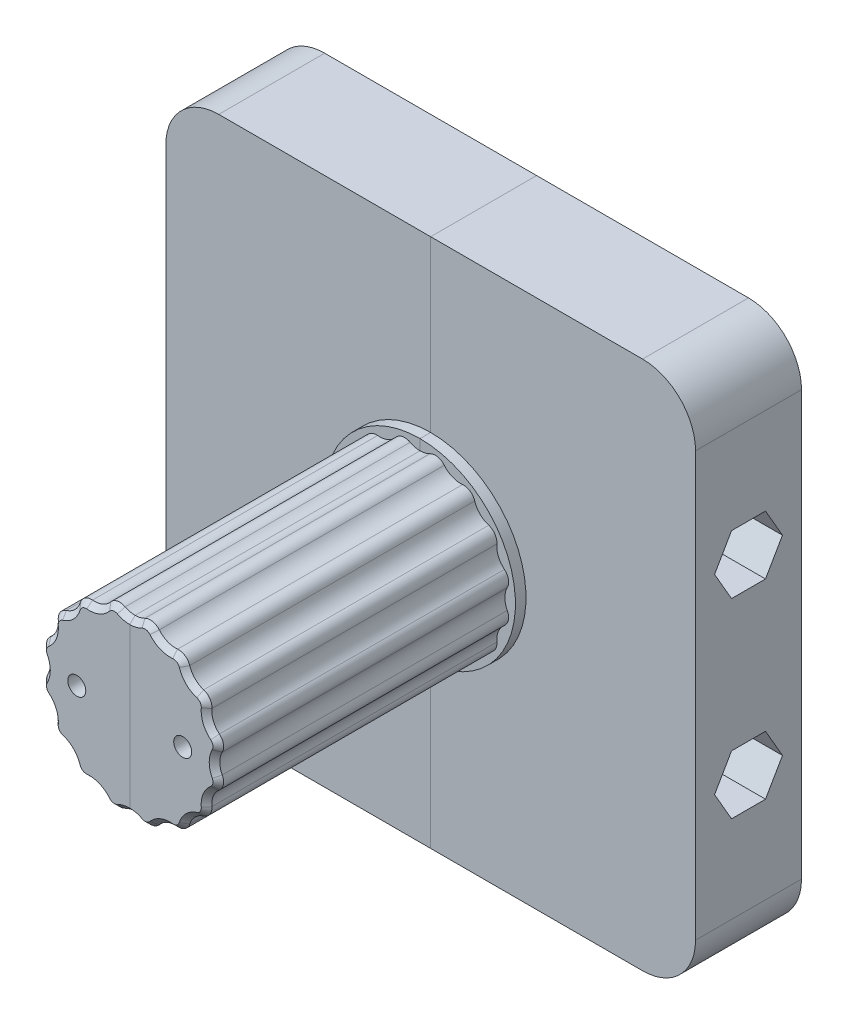
SolidWorks part; units mm, degrees
ref_plane "Plan de face" through (0, 0, 0) normal (0, 0, 1) x (1, 0, 0)
ref_plane "Plan de dessus" through (0, 0, 0) normal (0, 1, 0) x (1, 0, 0)
ref_plane "Plan de droite" through (0, 0, 0) normal (1, 0, 0) x (0, 0, -1)
sketch "Esquisse1" plane through (0, 0, 0) normal (0, 0, 1) x (1, 0, 0)
  line L1 (-25, -25) -> (25, -25)
  line L2 (-25, -25) -> (-25, 25)
  line L3 (-25, 25) -> (25, 25)
  line L4 (25, -25) -> (25, 25)
  line L5 (-25, -25) -> (25, 25) construction
  line L6 (-25, 25) -> (25, -25) construction
  point P0 (0, 0)
  dimension "D2" = 50
  dimension "D3" = 50
extrude "Boss.-Extru.1" add sketch "Esquisse1" along normal blind 10
sketch "Esquisse2" plane through (0, 0, 10) normal (0, 0, 1) x (1, 0, 0)
  circle A0 centre (0, 0) radius 9
  dimension "D1" = 18
extrude "Boss.-Extru.2" add sketch "Esquisse2" along normal blind 1
sketch "Esquisse5" plane through (0, 0, 10) normal (0, 0, 1) x (1, 0, 0)
  circle A0 centre (0, 0) radius 8.5
  dimension "D1" = 17
extrude "Boss.-Extru.3" add sketch "Esquisse5" along normal blind 27.4 from surface starting at face at (9, 0, 11)
sketch "Esquisse6" [suppressed] plane through (0, 0, 22) normal (0, 0, 1) x (1, 0, 0)
  line L0 (0, 2.5) -> (0, -2.5) construction
  line L1 (-1.5, 2) -> (-1.5, -2) construction
  line L3 (1.5, 2) -> (1.5, -2) construction
  line L4 (-1.6, 2.0494) -> (-1.6, -2.0494)
  line L5 (1.6, 2.0494) -> (1.6, -2.0494)
  arc A0 (-1.5, -2) -> (1.5, -2) centre (0, 0) ccw construction
  arc A1 (1.5, 2) -> (-1.5, 2) centre (0, 0) ccw construction
  arc A2 (-1.6, -2.0494) -> (1.6, -2.0494) centre (0, 0) ccw
  arc A3 (1.6, 2.0494) -> (-1.6, 2.0494) centre (0, 0) ccw
  dimension "D2" = 5
  dimension "D1" = 1.5
  dimension "D3" = 0.1
extrude "Enlèv. mat.-Extru.1" [suppressed] cut sketch "Esquisse6" against normal up to surface (12 mm away) up to face at (9, 0, 10)
sketch "Esquisse15" plane through (0, 0, 38.4) normal (0, 0, 1) x (1, 0, 0)
  line L0 (-1.3775, 1.45) -> (1.3775, 1.45) construction
  line L1 (-1.4169, 1.55) -> (1.4169, 1.55)
  arc A0 (-1.3775, 1.45) -> (1.3775, 1.45) centre (0, 0) ccw construction
  arc A1 (-1.4169, 1.55) -> (1.4169, 1.55) centre (0, 0) ccw
  point P5 (0, -2)
  dimension "D1" = 4
  dimension "D2" = 3.45
  dimension "D3" = 0.1
extrude "Enlèv. mat.-Extru.8" [suppressed] cut sketch "Esquisse15" against normal blind 10
sketch "Esquisse16" plane through (0, 0, 38.4) normal (0, 0, 1) x (1, 0, 0)
  line L0 (-5, 0) -> (5, 0) construction
  circle A0 centre (-5, 0) radius 0.85
  circle A1 centre (5, 0) radius 0.85
  point P4 (0, 0)
  dimension "D1" = 1.7
  dimension "D2" = 10
extrude "Enlèv. mat.-Extru.9" cut sketch "Esquisse16" against normal blind 10
sketch "Esquisse7" plane through (0, 0, 38.4) normal (0, 0, 1) x (1, 0, 0)
  arc A0 (-0.9333, 8.2311) -> (0.9333, 8.2311) centre (0, 10) ccw
  circle A1 centre (0, 0) radius 8.5 construction
  circle A2 centre (0, 0) radius 8.5 construction
  circle A3 centre (0, 0) radius 8.5 construction
  arc A4 (2.2876, 7.9617) -> (4.0122, 7.2474) centre (3.8268, 9.2388) ccw
  arc A5 (5.1603, 6.4802) -> (6.4802, 5.1603) centre (7.0711, 7.0711) ccw
  arc A6 (7.2474, 4.0122) -> (7.9617, 2.2876) centre (9.2388, 3.8268) ccw
  arc A7 (8.2311, 0.9333) -> (8.2311, -0.9333) centre (10, 0) ccw
  arc A8 (7.9617, -2.2876) -> (7.2474, -4.0122) centre (9.2388, -3.8268) ccw
  arc A9 (6.4802, -5.1603) -> (5.1603, -6.4802) centre (7.0711, -7.0711) ccw
  arc A10 (4.0122, -7.2474) -> (2.2876, -7.9617) centre (3.8268, -9.2388) ccw
  arc A11 (0.9333, -8.2311) -> (-0.9333, -8.2311) centre (0, -10) ccw
  arc A12 (-2.2876, -7.9617) -> (-4.0122, -7.2474) centre (-3.8268, -9.2388) ccw
  arc A13 (-5.1603, -6.4802) -> (-6.4802, -5.1603) centre (-7.0711, -7.0711) ccw
  arc A14 (-7.2474, -4.0122) -> (-7.9617, -2.2876) centre (-9.2388, -3.8268) ccw
  arc A15 (-8.2311, -0.9333) -> (-8.2311, 0.9333) centre (-10, 0) ccw
  arc A16 (-7.9617, 2.2876) -> (-7.2474, 4.0122) centre (-9.2388, 3.8268) ccw
  arc A17 (-6.4802, 5.1603) -> (-5.1603, 6.4802) centre (-7.0711, 7.0711) ccw
  arc A18 (-4.0122, 7.2474) -> (-2.2876, 7.9617) centre (-3.8268, 9.2388) ccw
  arc A19 (2.2876, 7.9617) -> (0.9333, 8.2311) centre (1.4445, 7.2622) ccw
  arc A20 (5.1603, 6.4802) -> (4.0122, 7.2474) centre (4.1137, 6.1566) ccw
  arc A21 (7.2474, 4.0122) -> (6.4802, 5.1603) centre (6.1566, 4.1137) ccw
  arc A22 (8.2311, 0.9333) -> (7.9617, 2.2876) centre (7.2622, 1.4445) ccw
  arc A23 (7.9617, -2.2876) -> (8.2311, -0.9333) centre (7.2622, -1.4445) ccw
  arc A24 (6.4802, -5.1603) -> (7.2474, -4.0122) centre (6.1566, -4.1137) ccw
  arc A25 (4.0122, -7.2474) -> (5.1603, -6.4802) centre (4.1137, -6.1566) ccw
  arc A26 (0.9333, -8.2311) -> (2.2876, -7.9617) centre (1.4445, -7.2622) ccw
  arc A27 (-2.2876, -7.9617) -> (-0.9333, -8.2311) centre (-1.4445, -7.2622) ccw
  arc A28 (-5.1603, -6.4802) -> (-4.0122, -7.2474) centre (-4.1137, -6.1566) ccw
  arc A29 (-7.2474, -4.0122) -> (-6.4802, -5.1603) centre (-6.1566, -4.1137) ccw
  arc A30 (-8.2311, -0.9333) -> (-7.9617, -2.2876) centre (-7.2622, -1.4445) ccw
  arc A31 (-7.9617, 2.2876) -> (-8.2311, 0.9333) centre (-7.2622, 1.4445) ccw
  arc A32 (-6.4802, 5.1603) -> (-7.2474, 4.0122) centre (-6.1566, 4.1137) ccw
  arc A33 (-4.0122, 7.2474) -> (-5.1603, 6.4802) centre (-4.1137, 6.1566) ccw
  arc A34 (-0.9333, 8.2311) -> (-2.2876, 7.9617) centre (-1.4445, 7.2622) ccw
  circle A37 centre (0, 0) radius 9.904
  point P2 (0, 8)
  point P5 (0, 8.5)
  point P43 (0, 0)
  point P75 (0, 0)
  dimension "D1" = 4
  dimension "D2" = 0.5
  dimension "D3" = 16
  dimension "D4" = 16
extrude "Enlèv. mat.-Extru.2" cut sketch "Esquisse7" against normal up to surface (27.4 mm away) up to face at (8.5, 0, 11)
chamfer "Chanfrein1" distance 0.5 angle 45 32 edges at (3.0615, 7.391, 38.4) (1.6583, 8.3367, 38.4) (4.7223, 7.0675, 38.4) (0, 8, 38.4) (5.6569, 5.6569, 38.4) (-1.6583, 8.3367, 38.4) (7.0675, 4.7223, 38.4) (-3.0615, 7.391, 38.4) (7.391, 3.0615, 38.4) (-4.7223, 7.0675, 38.4) (8.3367, 1.6583, 38.4) (-5.6569, 5.6569, 38.4) (8, 0, 38.4) (-7.0675, 4.7223, 38.4) (8.3367, -1.6583, 38.4) (-7.391, 3.0615, 38.4) (7.391, -3.0615, 38.4) (-8.3367, 1.6583, 38.4) (7.0675, -4.7223, 38.4) (-8, 0, 38.4) (5.6569, -5.6569, 38.4) (-8.3367, -1.6583, 38.4) (4.7223, -7.0675, 38.4) (-7.391, -3.0615, 38.4) (3.0615, -7.391, 38.4) (-7.0675, -4.7223, 38.4) (1.6583, -8.3367, 38.4) (-5.6569, -5.6569, 38.4) (0, -8, 38.4) (-4.7223, -7.0675, 38.4) (-1.6583, -8.3367, 38.4) (-3.0615, -7.391, 38.4)
sketch "Esquisse8" plane through (0, 0, 0) normal (0, 0, -1) x (-1, 0, 0)
  line L4 (-25, 25) -> (-25, -25)
  line L5 (-25, -25) -> (25, -25)
  line L6 (25, -25) -> (25, 25)
  line L7 (25, 25) -> (-25, 25)
  line L8 (-25, 25) -> (-25, -25)
  line L9 (-25, -25) -> (25, -25)
  line L10 (25, -25) -> (25, 25)
  line L11 (25, 25) -> (-25, 25)
  dimension "D1" = 0
extrude "Enlèv. mat.-Extru.3" [suppressed] cut sketch "Esquisse8" against normal offset from surface (2 mm away) 3 up to face at (9, 0, 10)
sketch "Esquisse9" [suppressed] plane through (0, 0, 2) normal (0, 0, -1) x (-1, 0, 0)
  line L4 (25, 25) -> (-25, 25)
  line L5 (-25, 25) -> (-25, -25)
  line L6 (-25, -25) -> (25, -25)
  line L7 (25, -25) -> (25, 25)
  line L8 (25, 25) -> (-25, 25)
  line L9 (-25, 25) -> (-25, -25)
  line L10 (-25, -25) -> (25, -25)
  line L11 (25, -25) -> (25, 25)
  circle A0 centre (0, 0) radius 22.5
  dimension "D1" = 45
  dimension "D2" = 0
extrude "Enlèv. mat.-Extru.4" [suppressed] cut sketch "Esquisse9" against normal blind 3
fillet "Congé1" radius 5 4 edges at (-25, -25, 5) (-25, 25, 5) (25, 25, 5) (25, -25, 5)
sketch "Esquisse10" plane through (0, 0, 0) normal (0, 0, -1) x (-1, 0, 0)
  circle A0 centre (0, 0) radius 2.15
  dimension "D1" = 4.3
extrude "Enlèv. mat.-Extru.5" cut sketch "Esquisse10" against normal blind 8
split "Fractionner1" bodies to split 109 resulting bodies 112 113 split by face at (-2.15, 0, 8)
sketch "Esquisse13" plane through (0, 0, 0) normal (0, 0, -1) x (-1, 0, 0)
  circle A0 centre (0, 0) radius 2.15 construction
  circle A1 centre (0, 0) radius 2.15
curve "Hélice/Spirale1" pitch 1.27 height 10 radius 2.15 centre (0, 0, 0) axis (0, 0, 1) start towards (-1, 0, 0)
chamfer "Chanfrein3" distance 1.5 angle 45 1 edges at (-2.15, 0, 0)
sketch "Esquisse14" plane through (0, 0, 0) normal (0, 1, 0) x (1, 0, 0)
  line L0 (0, -12.1883) -> (0, 6.2203) construction
  line L1 (-2.15, -11.7343) -> (-2.15, 4.6609) construction
  line L2 (-20, 0) -> (20, 0) construction
  line L3 (-2.15, 0.3175) -> (-2.8374, 0.7144) construction
  line L4 (-2.8374, 0.7144) -> (-2.8374, 0.8731) construction
  line L5 (-2.8374, 0.8731) -> (-2.15, 1.27) construction
  line L6 (-2.15, 1.27) -> (-2.15, 0.3175) construction
  line L7 (-1.95, 1.6164) -> (-1.95, 0)
  line L8 (-2.35, 0.202) -> (-3.0374, 0.5989)
  line L10 (-3.0374, 0.9886) -> (-1.95, 1.6164)
  line L11 (-2.35, 0) -> (-2.35, 0.202)
  line L12 (-2.35, 0) -> (-1.95, 0)
  line L13 (-2.35, -11.7343) -> (-2.35, 2.9925) construction
  line L14 (-1.95, -0.0289) -> (-3.0374, 0.5989) construction
  line L15 (-1.95, 1.6164) -> (-1.95, -0.0289) construction
  line L16 (-2.15, -11.7343) -> (-2.15, 2.9925) construction
  line L17 (-3.0374, 0.5989) -> (-3.0374, 0.9886) construction
  arc A0 (-3.0374, 0.5989) -> (-3.0374, 0.9886) centre (-2.9249, 0.7938) cw
  spline S0 degree 3 poles (-2.15, 0) (-2.15, -0.0265) (-2.0363, -0.0801) (-1.5508, -0.16) (-0.8256, -0.24) (0.0273, -0.32) (0.876, -0.4) (1.5892, -0.48) (2.0567, -0.56) (2.2062, -0.64) (2.0146, -0.72) (1.5115, -0.8) (0.7747, -0.88) (-0.0819, -0.96) (-0.9258, -1.04) (-1.6266, -1.12) (-2.0758, -1.2) (-2.2042, -1.28) (-1.9917, -1.36) (-1.4713, -1.44) (-0.7234, -1.52) (0.1364, -1.6) (0.9751, -1.68) (1.663, -1.76) (2.0937, -1.84) (2.2008, -1.92) (1.9676, -2) (1.4301, -2.08) (0.6716, -2.16) (-0.1908, -2.24) (-1.0237, -2.32) (-1.6983, -2.4) (-2.1104, -2.48) (-2.1961, -2.56) (-1.9422, -2.64) (-1.3881, -2.72) (-0.6194, -2.8) (0.2452, -2.88) (1.0718, -2.96) (1.7327, -3.04) (2.1257, -3.12) (2.19, -3.2) (1.9157, -3.28) (1.3453, -3.36) (0.5668, -3.44) (-0.2993, -3.52) (-1.1192, -3.6) (-1.7659, -3.68) (-2.1397, -3.76) (-2.1826, -3.84) (-1.8881, -3.92) (-1.3016, -4) (-0.5139, -4.08) (0.3533, -4.16) (1.1659, -4.24) (1.7981, -4.32) (2.1524, -4.4) (2.1739, -4.48) (1.8592, -4.56) (1.2571, -4.64) (0.4606, -4.72) (-0.4071, -4.8) (-1.2118, -4.88) (-1.8292, -4.96) (-2.1638, -5.04) (-2.1638, -5.12) (-1.8292, -5.2) (-1.2118, -5.28) (-0.4071, -5.36) (0.4606, -5.44) (1.2571, -5.52) (1.8592, -5.6) (2.1739, -5.68) (2.1524, -5.76) (1.7981, -5.84) (1.1659, -5.92) (0.3533, -6) (-0.5139, -6.08) (-1.3016, -6.16) (-1.8881, -6.24) (-2.1826, -6.32) (-2.1397, -6.4) (-1.7659, -6.48) (-1.1192, -6.56) (-0.2993, -6.64) (0.5668, -6.72) (1.3453, -6.8) (1.9157, -6.88) (2.19, -6.96) (2.1257, -7.04) (1.7327, -7.12) (1.0718, -7.2) (0.2452, -7.28) (-0.6194, -7.36) (-1.3881, -7.44) (-1.9422, -7.52) (-2.1961, -7.6) (-2.1104, -7.68) (-1.6983, -7.76) (-1.0237, -7.84) (-0.1908, -7.92) (0.6716, -8) (1.4301, -8.08) (1.9676, -8.16) (2.2008, -8.24) (2.0937, -8.32) (1.663, -8.4) (0.9751, -8.48) (0.1364, -8.56) (-0.7234, -8.64) (-1.4713, -8.72) (-1.9917, -8.8) (-2.2042, -8.88) (-2.0758, -8.96) (-1.6266, -9.04) (-0.9258, -9.12) (-0.0819, -9.2) (0.7747, -9.28) (1.5115, -9.36) (2.0146, -9.44) (2.2062, -9.52) (2.0567, -9.6) (1.5892, -9.68) (0.876, -9.76) (0.0271, -9.84) (-0.825, -9.9199) (-1.3103, -9.9735) (-1.5108, -10) knots 0 0 0 0 0.008 0.016 0.024 0.032 0.04 0.048 0.056 0.064 0.072 0.08 0.088 0.096 0.104 0.112 0.12 0.128 0.136 0.144 0.152 0.16 0.168 0.176 0.184 0.192 0.2 0.208 0.216 0.224 0.232 0.24 0.248 0.256 0.264 0.272 0.28 0.288 0.296 0.304 0.312 0.32 0.328 0.336 0.344 0.352 0.36 0.368 0.376 0.384 0.392 0.4 0.408 0.416 0.424 0.432 0.44 0.448 0.456 0.464 0.472 0.48 0.488 0.496 0.504 0.512 0.52 0.528 0.536 0.544 0.552 0.56 0.568 0.576 0.584 0.592 0.6 0.608 0.616 0.624 0.632 0.64 0.648 0.656 0.664 0.672 0.68 0.688 0.696 0.704 0.712 0.72 0.728 0.736 0.744 0.752 0.76 0.768 0.776 0.784 0.792 0.8 0.808 0.816 0.824 0.832 0.84 0.848 0.856 0.864 0.872 0.88 0.888 0.896 0.904 0.912 0.92 0.928 0.936 0.944 0.952 0.96 0.968 0.976 0.984 0.992 1 1 1 1 construction
  point P5 (-2.15, 0)
  point P24 (-2.3, 4.6609)
  point P27 (0, 0)
  point P28 (0, 0)
  dimension "D1" = 60
  dimension "D2" = 1.27
  dimension "D3" = 0.3175
  dimension "D4" = 0.1588
  dimension "D5" = 0.2
  dimension "D6" = 0.2
sweep "Enlèvement de matière-Balayage1" cut profiles "Esquisse14" path "Hélice/Spirale1" align with end faces yes
combine bodies "Combiner1" operation type add bodies to combine 114 113
sketch "Esquisse11" plane through (0, 0, 0) normal (0, 0, -1) x (-1, 0, 0)
  circle A0 centre (0, 14) radius 2.25
  dimension "D1" = 4.5
  dimension "D2" = 14
extrude "Enlèv. mat.-Extru.6" cut sketch "Esquisse11" against normal blind 5
chamfer "Chanfrein2" distance 2 angle 45 1 edges at (-2.25, 14, 5)
chamfer "Chanfrein4" distance 1 angle 45 1 edges at (-2.25, 14, 0)
sketch "Esquisse12" plane through (0, 0, 10) normal (0, 0, 1) x (1, 0, 0)
  line L4 (-25, 20) -> (-25, -20)
  line L5 (-20, -25) -> (20, -25)
  line L6 (25, -20) -> (25, 20)
  line L7 (20, 25) -> (-20, 25)
  line L8 (-25, 20) -> (-25, -20)
  line L9 (-20, -25) -> (20, -25)
  line L10 (25, -20) -> (25, 20)
  line L11 (20, 25) -> (-20, 25)
  arc A4 (-25, -20) -> (-20, -25) centre (-20, -20) ccw
  arc A5 (20, -25) -> (25, -20) centre (20, -20) ccw
  arc A6 (25, 20) -> (20, 25) centre (20, 20) ccw
  arc A7 (-20, 25) -> (-25, 20) centre (-20, 20) ccw
  arc A8 (-25, -20) -> (-20, -25) centre (-20, -20) ccw
  arc A9 (20, -25) -> (25, -20) centre (20, -20) ccw
  arc A10 (25, 20) -> (20, 25) centre (20, 20) ccw
  arc A11 (-20, 25) -> (-25, 20) centre (-20, 20) ccw
  dimension "D1" = 0
extrude "Enlèv. mat.-Extru.7" [suppressed] cut sketch "Esquisse12" against normal through all
sketch "Sketch3" plane through (0, 0, 38.4) normal (0, 0, 1) x (1, 0, 0)
  circle A0 centre (0, 0) radius 4.6
  circle A1 centre (0, 0) radius 3
  dimension "D1" = 9.2
  dimension "D2" = 6
sketch "Sketch1" plane through (0, 0, 38.4) normal (0, 0, 1) x (1, 0, 0)
  circle A0 centre (0, 0) radius 3
  dimension "D1" = 6
extrude "Cut-Extrude1" [suppressed] cut sketch "Sketch1" against normal blind 6.1 from surface
sketch "Sketch2" plane through (0, 0, 0) normal (0, 0, 1) x (1, 0, 0)
  circle A0 centre (0, 0) radius 8.5
  arc A1 (8.2311, 0.9333) -> (7.9617, 2.2876) centre (7.2622, 1.4445) ccw construction
extrude "Boss-Extrude1" [suppressed] add sketch "Sketch2" against normal blind 2 from surface
fillet "Fillet1" [suppressed] radius 0.6
sketch "Sketch4" plane through (0, 0, 0) normal (0, 0, -1) x (-1, 0, 0)
  line L12 (-9, -9) -> (9, -9)
  line L13 (9, -9) -> (9, 9)
  line L14 (9, 9) -> (-9, 9)
  line L15 (-9, 9) -> (-9, -9)
  line L16 (-4, -9) -> (4, -9)
  line L17 (9, -4) -> (9, 4)
  line L18 (4, 9) -> (-4, 9)
  line L19 (-9, 4) -> (-9, -4)
  arc A8 (-4, -9) -> (-9, -4) centre (-4, -4) cw
  arc A9 (4, -9) -> (9, -4) centre (4, -4) ccw
  arc A10 (9, 4) -> (4, 9) centre (4, 4) ccw
  arc A11 (-4, 9) -> (-9, 4) centre (-4, 4) ccw
  dimension "D2" = 5
  dimension "D1" = 16
extrude "Cut-Extrude3" cut sketch "Sketch4" against normal blind 1
sketch "Sketch5" plane through (0, 0, 0) normal (1, 0, 0) x (0, 0, -1)
  line L0 (-5, 25) -> (-5, -25) construction
  line L1 (-10, 25) -> (0, 25) construction
  line L2 (0, -25) -> (-10, -25) construction
  line L3 (0, 0) -> (-37.9, 0) construction
  line L4 (-37.9, 0.9333) -> (-37.9, -0.9333) construction
  line L6 (-8.2043, 9) -> (-6.6021, 6.225)
  line L7 (-6.6021, 6.225) -> (-3.3979, 6.225)
  line L8 (-3.3979, 6.225) -> (-1.7957, 9)
  line L9 (-1.7957, 9) -> (-3.3979, 11.775)
  line L10 (-3.3979, 11.775) -> (-6.6021, 11.775)
  line L11 (-6.6021, 11.775) -> (-8.2043, 9)
  line L12 (-8.2043, -9) -> (-6.6021, -11.775)
  line L13 (-6.6021, -11.775) -> (-3.3979, -11.775)
  line L14 (-3.3979, -11.775) -> (-1.7957, -9)
  line L15 (-1.7957, -9) -> (-3.3979, -6.225)
  line L16 (-3.3979, -6.225) -> (-6.6021, -6.225)
  line L17 (-6.6021, -6.225) -> (-8.2043, -9)
  circle A0 centre (-5, 19) radius 0.9
  circle A1 centre (-5, -19) radius 0.9
  circle A2 centre (-5, 9) radius 1.6
  circle A3 centre (-5, -9) radius 1.6
  circle A4 centre (-33.9, 0) radius 0.9
  circle A5 centre (-18.9, 0) radius 0.9
  circle A6 centre (-5, 9) radius 3
  circle A7 centre (-5, -9) radius 3
  circle A8 centre (-5, 9) radius 2.775 construction
  circle A9 centre (-5, -9) radius 2.775 construction
  point P6 (-5, 0)
  dimension "D3" = 1.8
  dimension "D8" = 3.2
  dimension "D9" = 6
  dimension "D1" = 19
  dimension "D2" = 19
  dimension "D4" = 9
  dimension "D5" = 9
  dimension "D6" = 15
  dimension "D7" = 4
  dimension "D10" = 5.55
extrude "Cut-Extrude4" cut sketch "Sketch5" against normal mid plane 7 contours A4 | A5
extrude "Cut-Extrude6" cut sketch "Sketch5<4>" against normal mid plane 20 contours A2 | A3
sketch "Sketch5<4>" plane through (0, 0, 0) normal (1, 0, 0) x (0, 0, -1) same geometry as "Sketch5"
extrude "Cut-Extrude7" cut sketch "Sketch5<6>" against normal through all from surface contours A7 | A6 starting at face at (-10, -9, 3.4)
sketch "Sketch5<6>" plane through (0, 0, 0) normal (1, 0, 0) x (0, 0, -1) same geometry as "Sketch5"
extrude "Cut-Extrude8" cut sketch "Sketch5<9>" along normal through all from surface contours L6 L7 L8 L9 L10 L11 | L16 L17 L12 L13 L14 L15 starting at face at (10, 9, 3.4)
sketch "Sketch5<9>" plane through (0, 0, 0) normal (1, 0, 0) x (0, 0, -1) same geometry as "Sketch5"
split "Split1" trim tools "Plan de droite" bodies to split 129 resulting bodies 124 125
equation "\"D5@Esquisse14\"=\"D6@Esquisse14\""
equation "\"H\" = 40"
equation "\"D1\"= \"H\""
equation "\"external_diameter\"=100"
equation "\"external_bearing_diameter\"=22.85"
equation "\"internal_bearing_diameter\"=17"
equation "\"holes_patter_diameter\"=90"
equation "\"3mm_holes\"=2.9"
equation "\"D1@Esquisse5\"=\"internal_bearing_diameter\""
equation "\"D2@Sketch5\"=\"D1@Sketch5\""
equation "\"D5@Sketch5\"=\"D4@Sketch5\""
equation "\"ha\"= 27.4"
equation "\"D1@Boss.-Extru.3\"=\"ha\""
